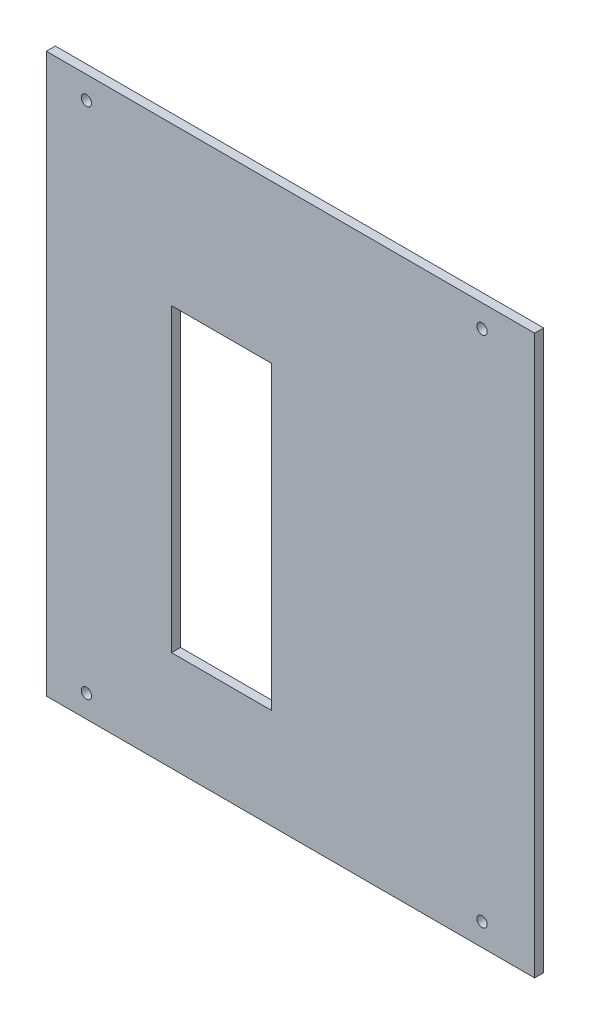
SolidWorks part; units mm, degrees
ref_plane "Plan de face" through (0, 0, 0) normal (0, 0, 1) x (1, 0, 0)
ref_plane "Plan de dessus" through (0, 0, 0) normal (0, 1, 0) x (1, 0, 0)
ref_plane "Plan de droite" through (0, 0, 0) normal (1, 0, 0) x (0, 0, -1)
sketch "Esquisse1" plane through (0, 0, 0) normal (0, 0, 1) x (1, 0, 0)
  line L0 (0, 138.1871) -> (0, -161.4958) construction
  line L12 (75, -111.5) -> (-120, -111.5)
  line L13 (-211.9518, 0) -> (287.0439, 0) construction
  line L18 (80, 170.0365) -> (80, -138.99) construction
  line L19 (-80, 170.0365) -> (-80, -138.99) construction
  line L20 (75, -111.5) -> (75, 111.5)
  line L21 (75, 111.5) -> (-120, 111.5)
  line L22 (-120, -111.5) -> (-120, 111.5)
  line L23 (75, -111.5) -> (-120, 111.5) construction
  line L24 (75, 111.5) -> (-120, -111.5) construction
  line L25 (75, -112.5) -> (-120, -112.5) construction
  line L26 (75, -112.5) -> (75, 112.5) construction
  line L27 (75, 112.5) -> (-120, 112.5) construction
  line L28 (-120, -112.5) -> (-120, 112.5) construction
  line L29 (75, -112.5) -> (-120, 112.5) construction
  line L30 (75, 112.5) -> (-120, -112.5) construction
  line L31 (-30, -71.5) -> (-70, -71.5)
  line L32 (-30, -71.5) -> (-30, 48.5)
  line L33 (-30, 48.5) -> (-70, 48.5)
  line L34 (-70, -71.5) -> (-70, 48.5)
  line L35 (-30, -71.5) -> (-70, 48.5) construction
  line L36 (-30, 48.5) -> (-70, -71.5) construction
  circle A0 centre (-104, 102.5) radius 2.05
  circle A1 centre (54, 102.5) radius 2.05
  circle A2 centre (54, -102.5) radius 2.05
  circle A3 centre (-104, -102.5) radius 2.05
  point P0 (0, 0)
  point P1 (-22.5, 0)
  point P5 (0, 0)
  point P9 (-22.5, 0)
  point P30 (-50, -11.5)
  dimension "D2" = 4.1
  dimension "D1" = 195
  dimension "D3" = 26
  dimension "D4" = 24
  dimension "D5" = 223
  dimension "D6" = 5
  dimension "D7" = 10
  dimension "D8" = 225
  dimension "D9" = 160
  dimension "D10" = 195
  dimension "D11" = 50
  dimension "D12" = 40
  dimension "D13" = 120
  dimension "D14" = 40
extrude "Boss.-Extru.1" add sketch "Esquisse1" along normal blind 3.6
